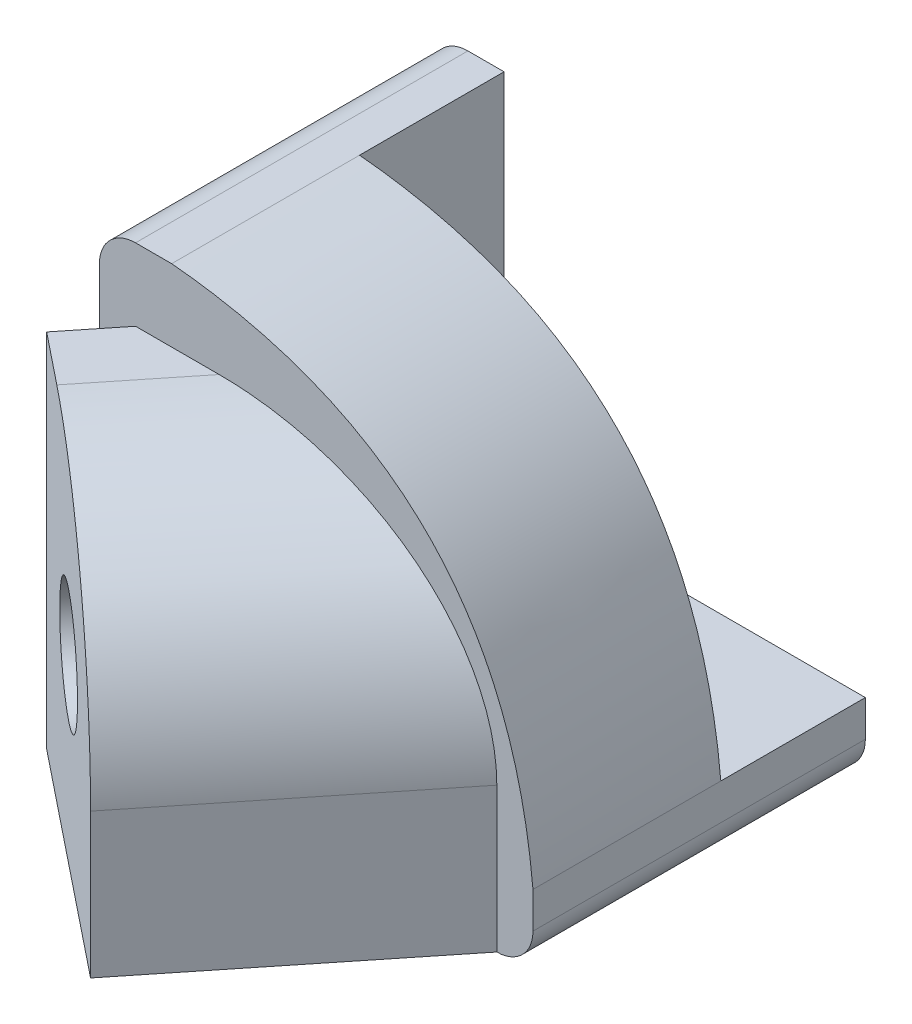
SolidWorks part; units mm, degrees
ref_plane "Front Plane" through (0, 0, 0) normal (0, 0, 1) x (1, 0, 0)
ref_plane "Top Plane" through (0, 0, 0) normal (0, 1, 0) x (1, 0, 0)
ref_plane "Right Plane" through (0, 0, 0) normal (1, 0, 0) x (0, 0, -1)
sketch "Sketch1" plane through (0, 0, 0) normal (0, 0, 1) x (1, 0, 0)
  line L0 (0, 0) -> (12.7, 0)
  line L1 (0, 0) -> (0, 12.7)
  circle A0 centre (5.08, 5.08) radius 3.1115
  spline S0 degree 2 poles (0, 12.7) (11.6203, 11.6203) (12.7, 0) knots 0 0 0 1 1 1
  dimension "D5" = 6.223
  dimension "D1" = 12.7
  dimension "D2" = 12.7
  dimension "D3" = 5.08
  dimension "D4" = 5.08
extrude "Boss-Extrude1" add sketch "Sketch1" along normal blind 3.81
sketch "Sketch2" plane through (0, 0, 0) normal (0, 0, -1) x (-1, 0, 0)
  line L0 (0, 12.7) -> (1.27, 12.7)
  line L1 (2.54, 11.43) -> (2.54, -1.27)
  line L2 (0, 12.7) -> (0, 0) construction
  line L3 (-12.7, 0) -> (-12.7, -1.27)
  line L4 (-11.43, -2.54) -> (1.27, -2.54)
  line L5 (0, 12.7) -> (0, 0)
  line L6 (0, 0) -> (-12.7, 0)
  arc A0 (1.27, 12.7) -> (2.54, 11.43) centre (1.27, 11.43) cw
  arc A1 (-12.7, -1.27) -> (-11.43, -2.54) centre (-11.43, -1.27) ccw
  arc A2 (1.27, -2.54) -> (2.54, -1.27) centre (1.27, -1.27) ccw
  point P14 (-12.7, -2.54)
  dimension "D3" = 1.27
  dimension "D1" = 2.54
  dimension "D2" = 2.54
extrude "Boss-Extrude2" add sketch "Sketch2" along normal blind 5.08 and the other way blind 3.81 contours L1 A2 L4 A1 L3 L6 L5 L0 A0
sketch "Sketch3" plane through (0, 0, 3.81) normal (0, 0, 1) x (1, 0, 0)
  line L0 (-2.54, 11.43) -> (-2.54, -1.27)
  line L1 (-1.27, -2.54) -> (11.43, -2.54)
  line L2 (12.7, -1.27) -> (12.7, 0)
  line L3 (-1.27, 12.7) -> (0, 12.7)
  arc A0 (11.43, -2.54) -> (12.7, -1.27) centre (11.43, -1.27) ccw
  arc A1 (-2.54, 11.43) -> (-1.27, 12.7) centre (-1.27, 11.43) cw
  arc A3 (-2.54, -1.27) -> (-1.27, -2.54) centre (-1.27, -1.27) ccw
  spline S0 degree 2 poles (0, 12.7) (11.6203, 11.6203) (12.7, 0) knots 0 0 0 1 1 1
  dimension "D1" = 1.27
  dimension "D3" = 1.27
extrude "Boss-Extrude3" add sketch "Sketch3" along normal blind 0.254
sketch "Sketch4" plane through (0, 0, 4.064) normal (0, 0, 1) x (1, 0, 0)
  line L0 (-2.54, 11.43) -> (-2.54, -1.27)
  line L1 (-1.27, -2.54) -> (11.43, -2.54)
  line L2 (12.7, -1.27) -> (12.7, 0)
  line L3 (-1.27, 12.7) -> (0, 12.7)
  arc A0 (11.43, -2.54) -> (12.7, -1.27) centre (11.43, -1.27) ccw
  arc A1 (-2.54, 11.43) -> (-1.27, 12.7) centre (-1.27, 11.43) cw
  arc A3 (-2.54, -1.27) -> (-1.27, -2.54) centre (-1.27, -1.27) ccw
  spline S0 degree 2 poles (0, 12.7) (11.6203, 11.6203) (12.7, 0) knots 0 0 0 1 1 1
  dimension "D1" = 1.27
  dimension "D3" = 1.27
extrude "Boss-Extrude4" add sketch "Sketch4" along normal blind 2.54
sketch "Sketch9" plane through (0, -2.54, 0) normal (0, -1, 0) x (1, 0, 0)
  line L0 (-1.27, 6.604) -> (-2.6592, 8.3393)
  line L1 (-2.6592, 8.3393) -> (5.0803, 14.5354)
  line L2 (5.0803, 14.5354) -> (11.43, 6.604)
  line L3 (-1.27, 6.604) -> (-1.27, -5.08) construction
  line L4 (11.43, 6.604) -> (11.43, -5.08) construction
  line L5 (-1.27, 6.604) -> (11.43, 6.604)
  dimension "D1" = 141.32
  dimension "D2" = 141.32
  dimension "D3" = 10.16
extrude "Boss-Extrude5" add sketch "Sketch9" against normal blind 12.7 contours L2 L5 L0 L1
fillet "Fillet1" radius 7.62 1 edges at (8.2552, 10.16, 10.5697)
sketch "Sketch11" plane through (-5.1073, 0, 6.3795) normal (-0.625, 0, 0.7806) x (0.7806, 0, 0.625)
  line L0 (8.093, -2.54) -> (8.093, 13.7971) construction
  line L1 (3.1359, -2.54) -> (13.0501, -2.54) construction
  line L2 (3.1359, 3.81) -> (15.8556, 3.81) construction
  line L3 (3.1359, 10.16) -> (3.1359, -2.54) construction
  circle A0 centre (8.093, 3.81) radius 2
  point P6 (8.093, 3.81)
  dimension "D1" = 4
extrude "Cut-Extrude2" cut sketch "Sketch11" against normal blind 7 contours A0
